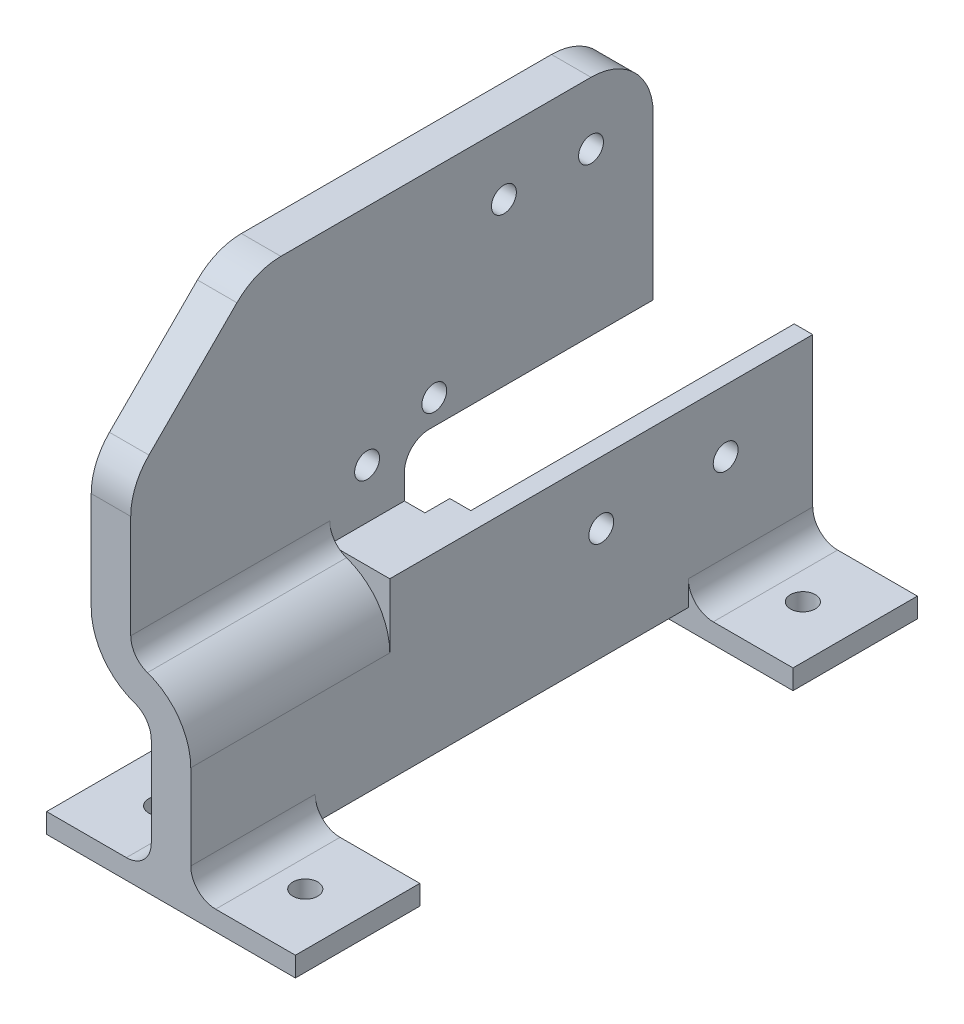
SolidWorks part; units mm, degrees
ref_plane "Front Plane" through (0, 0, 0) normal (0, 0, 1) x (1, 0, 0)
ref_plane "Top Plane" through (0, 0, 0) normal (0, 1, 0) x (1, 0, 0)
ref_plane "Right Plane" through (0, 0, 0) normal (1, 0, 0) x (0, 0, -1)
sketch "Sketch1" plane through (0, 0, 0) normal (0, 0, 1) x (1, 0, 0)
  line L0 (0, 0) -> (0, 110)
  line L1 (0, 110) -> (15.875, 110)
  line L2 (15.875, 110) -> (15.875, 0)
  line L3 (15.875, 0) -> (40, 0)
  line L4 (40, 0) -> (40, -70)
  line L5 (40, -70) -> (24.125, -70)
  line L6 (24.125, -70) -> (24.125, -15.875)
  line L7 (24.125, -15.875) -> (0, -15.875)
  line L8 (0, -15.875) -> (0, 0)
  point P9 (0, -7.9375)
  dimension "D1" = 15.875
  dimension "D2" = 70
  dimension "D3" = 180
  dimension "D4" = 40
extrude "Boss-Extrude1" add sketch "Sketch1" along normal blind 250
sketch "Sketch2" plane through (0, 0, 0) normal (0, 0, -1) x (-1, 0, 0)
  line L1 (-32.0625, -70) -> (-82.0625, -70)
  line L2 (17.9375, -70) -> (17.9375, -77.9375)
  line L3 (17.9375, -77.9375) -> (-82.0625, -77.9375)
  line L4 (-82.0625, -70) -> (-82.0625, -77.9375)
  line L5 (-24.125, -70) -> (-40, -70) construction
  line L6 (-32.0625, -70) -> (17.9375, -70)
  dimension "D1" = 100
  dimension "D2" = 7.9375
extrude "Boss-Extrude2" add sketch "Sketch2" against normal blind 50
sketch "Sketch3" plane through (0, -70, 0) normal (0, 1, 0) x (1, 0, 0)
  line L0 (61.0313, -50) -> (61.0313, 0) construction
  line L1 (40, -50) -> (82.0625, -50) construction
  line L2 (40, 0) -> (82.0625, 0) construction
  circle A0 centre (61.0313, -25) radius 5
extrude "Cut-Extrude1" cut sketch "Sketch3" against normal through all
ref_plane "Plane1" through (32.0625, 0, 0) normal (1, 0, 0) x (0, 0, -1)
mirror "Mirror1" about plane through (32.0625, 0, 0) normal (1, 0, 0) of "Cut-Extrude1"
fillet "Fillet1" radius 10 2 edges at (24.125, -70, 25) (40, -70, 25)
ref_plane "Plane2" through (0, 0, 125) normal (0, 0, -1) x (-1, 0, 0)
mirror "Mirror2" about plane through (0, 0, 125) normal (0, 0, -1) of "Fillet1", "Mirror1", "Boss-Extrude2", "Cut-Extrude1"
sketch "Sketch4" plane through (15.875, 0, 0) normal (1, 0, 0) x (0, 0, -1)
  line L0 (0, 0) -> (-140, 0)
  line L1 (-250, 0) -> (0, 0) construction
  line L2 (-140, 0) -> (-140, 20)
  line L3 (-140, 20) -> (-40, 20)
  line L4 (-40, 20) -> (-40, 110)
  line L5 (-250, 110) -> (0, 110) construction
  line L6 (-40, 110) -> (0, 110)
  line L7 (0, 110) -> (0, 0)
  dimension "D1" = 40
  dimension "D2" = 140
  dimension "D3" = 20
extrude "Cut-Extrude2" cut sketch "Sketch4" against normal through all
fillet "Fillet2" radius 25 1 edges at (7.9375, 110, 40)
sketch "Sketch5" plane through (15.875, 0, 0) normal (1, 0, 0) x (0, 0, -1)
  line L0 (-250, 60) -> (-250, 110)
  line L1 (-250, 0) -> (-250, 110) construction
  line L2 (-250, 110) -> (-200, 110)
  line L3 (-250, 110) -> (-65, 110) construction
  line L4 (-200, 110) -> (-250, 60)
  dimension "D1" = 50
  dimension "D2" = 45
extrude "Cut-Extrude3" cut sketch "Sketch5" against normal through all
fillet "Fillet3" radius 25 2 edges at (7.9375, 60, 250) (7.9375, 110, 200)
sketch "Sketch6" plane through (40, 0, 0) normal (1, 0, 0) x (0, 0, -1)
  line L0 (-40, 85) -> (-40, 20) construction
  line L1 (-140, 20) -> (-140, 0) construction
  line L2 (-250, 0) -> (0, 0) construction
  line L3 (-40, 20) -> (-140, 20) construction
  line L4 (0, -60) -> (0, 0) construction
  circle A0 centre (-65, 85) radius 5
  circle A1 centre (-100, 85) radius 5
  circle A2 centre (-128, 30) radius 5
  circle A3 centre (-155, 20) radius 5
  circle A4 centre (-35, -25) radius 5
  circle A5 centre (-85, -25) radius 5
  point P19 (-155, 20)
  point P22 (0, 0)
  point P23 (0, 0)
  point P24 (0, 0)
  dimension "D5" = 10
  dimension "D8" = 35
  dimension "D1" = 35
  dimension "D2" = 88
  dimension "D3" = 15
  dimension "D4" = 25
  dimension "D6" = 10
  dimension "D7" = 50
extrude "Cut-Extrude4" cut sketch "Sketch6" against normal through all
sketch "Sketch7" plane through (0, 0, 0) normal (0, 0, -1) x (-1, 0, 0)
  line L0 (0, 0) -> (-40, 0)
  line L1 (-40, 0) -> (-40, -40)
  line L2 (-40, -60) -> (-40, 0) construction
  line L3 (-40, -40) -> (-24.125, -40)
  line L4 (-24.125, -15.875) -> (-24.125, -60) construction
  line L5 (-24.125, -40) -> (-24.125, -15.875)
  line L6 (-24.125, -15.875) -> (0, -15.875)
  line L7 (0, -15.875) -> (0, 0)
  dimension "D1" = 40
extrude "Cut-Extrude5" cut sketch "Sketch7" against normal blind 170
fillet "Fillet4" radius 10 1 edges at (7.9375, 20, 140)
fillet "Fillet5" radius 25.875 1 edges at (40, 0, 210)
fillet "Fillet6" radius 10 1 edges at (15.875, 0, 210)
sketch "Sketch8" plane through (0, 0, 170) normal (0, 0, -1) x (-1, 0, 0)
  line L0 (-40, -40) -> (-24.125, -40)
  line L1 (-24.125, -40) -> (-24.125, -15.875)
  line L2 (-24.125, -15.875) -> (0, -15.875)
  line L3 (0, -15.875) -> (0, 0)
  line L4 (0, 0) -> (-40, 0)
  line L5 (-40, 0) -> (-40, -40)
extrude "Boss-Extrude3" add sketch "Sketch8" along normal up to vertex
sketch "Sketch9" plane through (0, 0, 140) normal (0, 0, -1) x (-1, 0, 0)
  line L1 (-40, 0) -> (-24.125, 0)
  line L2 (-40, 0) -> (-40, -40)
  line L3 (-40, -40) -> (-24.125, -40)
  line L4 (-24.125, 0) -> (-24.125, -40)
extrude "Boss-Extrude4" add sketch "Sketch9" along normal up to vertex (140 mm away)
fillet "Fillet7" radius 25.875 1 edges at (0, -15.875, 195)
fillet "Fillet8" radius 10 1 edges at (24.125, -15.875, 195)
sketch "Sketch10" plane through (0, 0, 0) normal (0, 0, -1) x (-1, 0, 0)
  line L1 (-24.125, 0) -> (-32.561, 0)
  line L2 (-24.125, 0) -> (-24.125, -40)
  line L3 (-24.125, -40) -> (-32.561, -40)
  line L4 (-32.561, 0) -> (-32.561, -40)
  dimension "D1" = 40
extrude "Cut-Extrude6" cut sketch "Sketch10" against normal blind 130
sketch "Sketch11" plane through (40, 0, 0) normal (1, 0, 0) x (0, 0, -1)
  line L1 (0, 0) -> (-170, 0) construction
  line L2 (0, -60) -> (0, 0) construction
  circle A0 centre (-35, -25) radius 5
  circle A1 centre (-85, -25) radius 5
  point P6 (0, 0)
  dimension "D1" = 10
  dimension "D2" = 25
  dimension "D3" = 50
  dimension "D4" = 35
extrude "Cut-Extrude7" cut sketch "Sketch11" against normal through all
